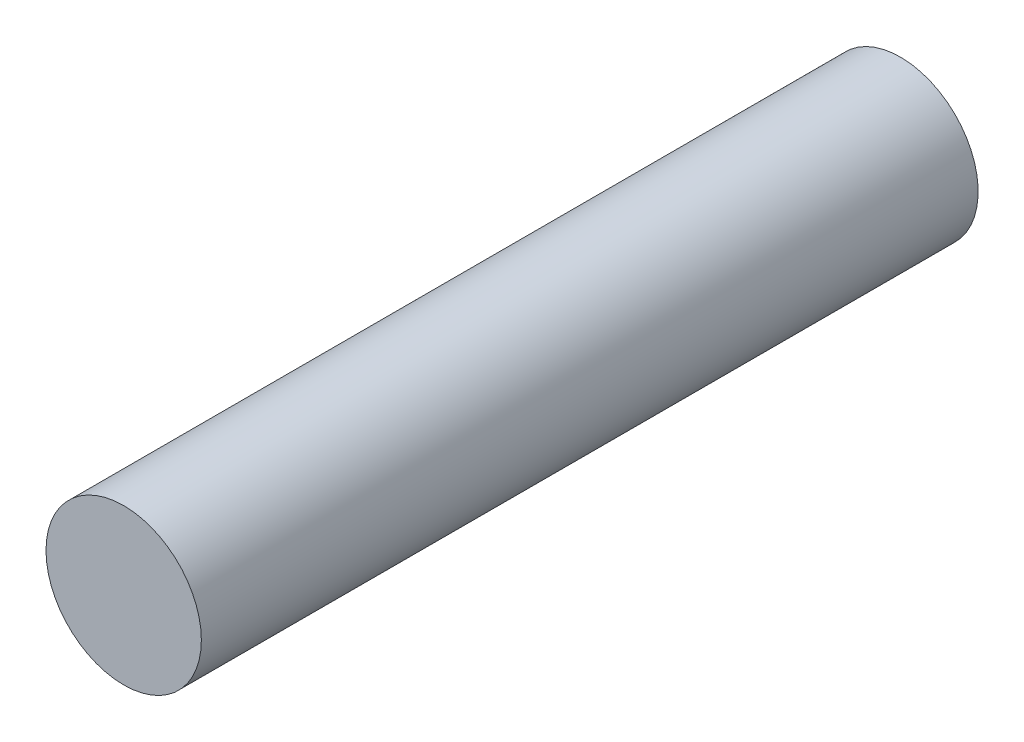
SolidWorks part; units mm, degrees
ref_plane "前视基准面" through (0, 0, 0) normal (0, 0, 1) x (1, 0, 0)
ref_plane "上视基准面" through (0, 0, 0) normal (0, 1, 0) x (1, 0, 0)
ref_plane "右视基准面" through (0, 0, 0) normal (1, 0, 0) x (0, 0, -1)
other "Configuration Table"
sketch "草图1" plane through (0, 0, 0) normal (0, 0, 1) x (1, 0, 0)
  circle A0 centre (0, 0) radius 5
  dimension "D1" = 10
extrude "凸台-拉伸1" add sketch "草图1" along normal blind 200
sketch "草图2" plane through (0, 0, 0) normal (0, 0, -1) x (-1, 0, 0)
  circle A0 centre (0, 0) radius 5
extrude "切除-拉伸1" cut sketch "草图2" against normal blind 150
